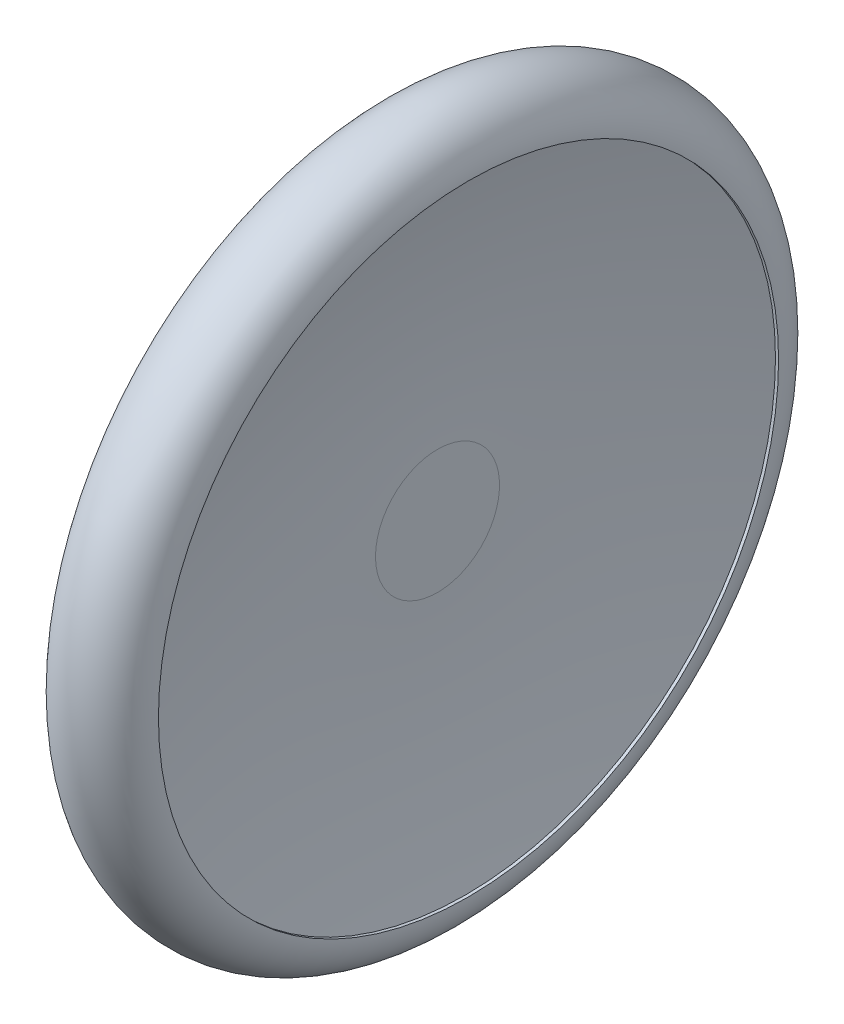
SolidWorks part; units mm, degrees
ref_plane "Front Plane" through (0, 0, 0) normal (0, 0, 1) x (1, 0, 0)
ref_plane "Top Plane" through (0, 0, 0) normal (0, 1, 0) x (1, 0, 0)
ref_plane "Right Plane" through (0, 0, 0) normal (1, 0, 0) x (0, 0, -1)
sketch "Sketch2" plane through (0, 0, 0) normal (0, 0, 1) x (1, 0, 0)
  line L4 (-5, 0) -> (5, 0)
  line L6 (-5, 0) -> (-5, 10)
  line L7 (-5, 10) -> (5, 10)
  line L8 (5, 0) -> (5, 10)
  line L9 (0, 0) -> (5, 10) construction
  line L10 (-5, 10) -> (0, 0) construction
  line L11 (-5, 50) -> (-5, 10)
  line L12 (9.5, 50) -> (10, 50)
  arc A0 (10, 50) -> (-5, 50) centre (2.5, 50) ccw
  arc A1 (5, 10) -> (9.5, 50) centre (185.0278, 10) cw
  point P3 (0, 0)
  dimension "D1" = 15
  dimension "D6" = 0.5
  dimension "D2" = 10
  dimension "D3" = 50
  dimension "D4" = 10
  dimension "D5" = 5
revolve "Revolve1" add sketch "Sketch2" angle 360 about L4 region at (0, 5, 0) region at (1.0944, 34.8296, 0)
sketch "Sketch3" plane through (-5, 0, 0) normal (-1, 0, 0) x (0, 0, 1)
  circle A0 centre (0, 0) radius 10
  dimension "D1" = 20
extrude "Boss-Extrude1" add sketch "Sketch3" along normal blind 10
ref_plane "Plane1" through (-10, 0, 0) normal (-1, 0, 0) x (0, 0, 1)
ref_axis "Axis1" through (-15, 0, 0) along (1, 0, 0)
ref_point "Point1"
